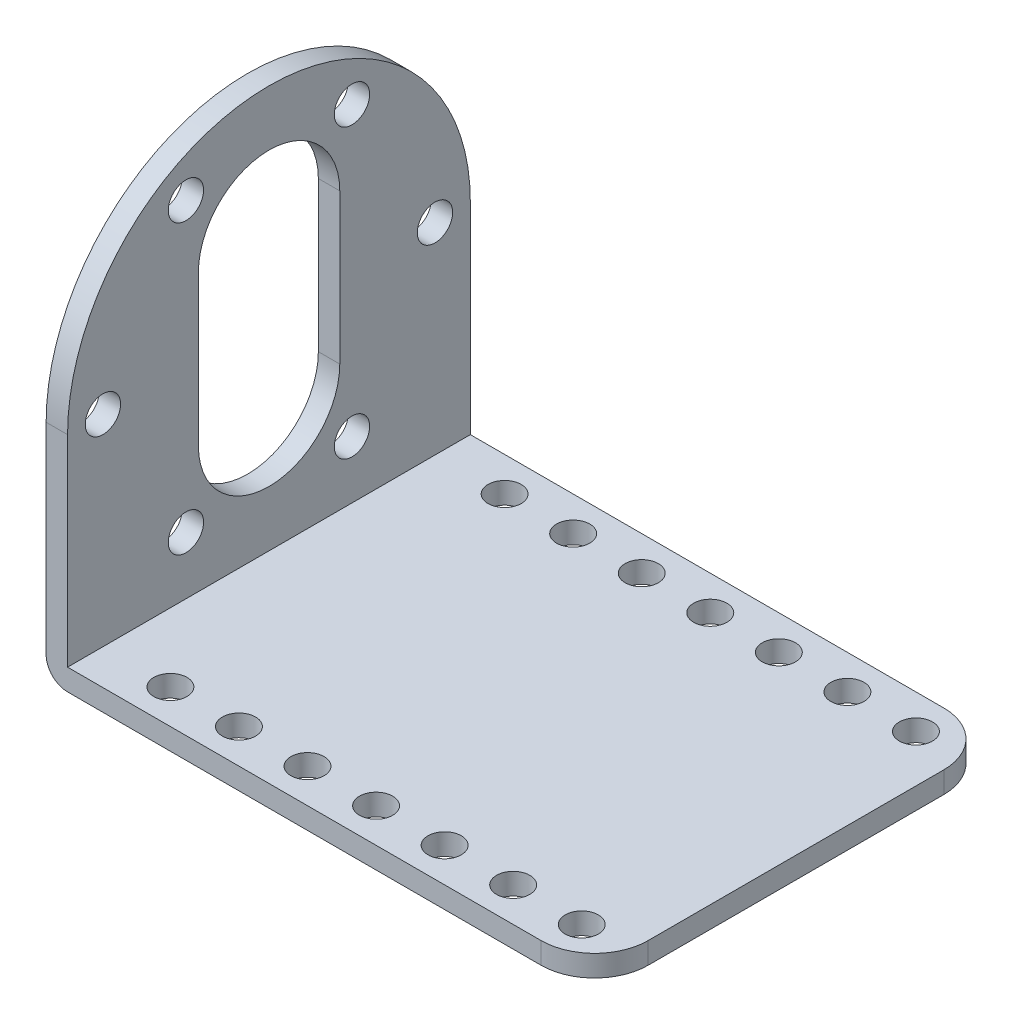
SolidWorks part; units mm, degrees
ref_plane "Front Plane" through (0, 0, 0) normal (0, 0, 1) x (1, 0, 0)
ref_plane "Top Plane" through (0, 0, 0) normal (0, 1, 0) x (1, 0, 0)
ref_plane "Right Plane" through (0, 0, 0) normal (1, 0, 0) x (0, 0, -1)
sketch "Sketch1" plane through (0, 0, 0) normal (0, 1, 0) x (1, 0, 0)
  line L1 (-58.1119, 10.0937) -> (-8.9119, 10.0937)
  line L2 (-58.1119, 10.0937) -> (-58.1119, -27.5063)
  line L3 (-58.1119, -27.5063) -> (-8.9119, -27.5063)
  line L4 (-8.9119, 10.0937) -> (-8.9119, -27.5063)
extrude "Boss-Extrude1" add sketch "Sketch1" along normal blind 2
ref_plane "Side plane L" through (0, 0, 27.5063) normal (0, 0, 1) x (1, 0, 0)
ref_plane "Top face plane" through (0, 2, 0) normal (0, 1, 0) x (1, 0, 0)
sketch "Sketch2" plane through (0, 2, 0) normal (0, 1, 0) x (1, 0, 0)
  line L0 (-1.1, -27.5063) -> (1.1, -27.5063) construction
  line L1 (-58.1119, 10.0937) -> (-60.1119, 10.0937)
  line L2 (-58.1119, 10.0937) -> (-58.1119, -27.5063)
  line L3 (-58.1119, -27.5063) -> (-60.1119, -27.5063)
  line L4 (-60.1119, 10.0937) -> (-60.1119, -27.5063)
extrude "Boss-Extrude2" add sketch "Sketch2" along normal blind 37.6 separate body
sketch "Sketch3" plane through (0, 0, 27.5063) normal (0, 0, 1) x (1, 0, 0)
  line L0 (20.68, 2) -> (-20.68, 2) construction
  line L1 (-58.1119, 2) -> (-58.1119, 0) construction
  line L2 (-60.1119, 2) -> (-58.1119, 2)
  line L3 (-58.1119, 2) -> (-58.1119, 0)
  arc A0 (-60.1119, 2) -> (-58.1119, 0) centre (-58.1119, 2) ccw
ref_plane "Side Plane R" through (0, 0, -10.0937) normal (0, 0, -1) x (-1, 0, 0)
extrude "Boss-Extrude5" add sketch "Sketch3" against normal blind 37.6 contours A0 L3 L2
sketch "Sketch4" plane through (0, 2, 0) normal (0, 1, 0) x (1, 0, 0)
  line L0 (-51.7119, 6.8937) -> (-58.1119, 6.8937) construction
  line L2 (-58.1119, -27.5063) -> (-58.1119, 10.0937) construction
  line L3 (-8.9119, -8.7063) -> (-58.1119, -8.7063) construction
  line L5 (-8.9119, -27.5063) -> (-8.9119, 10.0937) construction
  line L6 (-51.7119, -24.3063) -> (-51.7119, 6.8937) construction
  line L13 (-45.3119, -24.3063) -> (-45.3119, 6.8937) construction
  line L14 (-38.9119, -24.3063) -> (-38.9119, 6.8937) construction
  line L15 (-32.5119, -24.3063) -> (-32.5119, 6.8937) construction
  line L16 (-26.1119, -24.3063) -> (-26.1119, 6.8937) construction
  line L17 (-19.7119, -24.3063) -> (-19.7119, 6.8937) construction
  line L18 (-13.3119, -24.3063) -> (-13.3119, 6.8937) construction
  circle A0 centre (-51.7119, 6.8937) radius 1.55
  circle A1 centre (-51.7119, -24.3063) radius 1.55
  circle A2 centre (-45.3119, 6.8937) radius 1.55
  circle A3 centre (-38.9119, 6.8937) radius 1.55
  circle A4 centre (-32.5119, 6.8937) radius 1.55
  circle A5 centre (-26.1119, 6.8937) radius 1.55
  circle A6 centre (-19.7119, 6.8937) radius 1.55
  circle A7 centre (-13.3119, 6.8937) radius 1.55
  circle A8 centre (-13.3119, -24.3063) radius 1.55
  circle A9 centre (-19.7119, -24.3063) radius 1.55
  circle A10 centre (-26.1119, -24.3063) radius 1.55
  circle A11 centre (-32.5119, -24.3063) radius 1.55
  circle A12 centre (-38.9119, -24.3063) radius 1.55
  circle A13 centre (-45.3119, -24.3063) radius 1.55
  dimension "D1" = 7
extrude "Cut-Extrude1" cut sketch "Sketch4" against normal up to next
fillet "Fillet2" radius 5 2 edges at (-8.9119, 1, 27.5063) (-8.9119, 1, -10.0937)
sketch "Sketch5" plane through (-58.1119, 0, 0) normal (1, 0, 0) x (0, 0, -1)
  line L0 (-8.7063, 2) -> (-8.7063, 20.8) construction
  line L3 (-22.5063, 2) -> (5.0937, 2) construction
  line L4 (-27.5063, 39.6) -> (-27.5063, 2) construction
  line L5 (10.0937, 39.6) -> (10.0937, 2) construction
  circle A0 centre (-8.7063, 20.8) radius 15.5
  circle A1 centre (6.7937, 20.8) radius 1.65
  circle A2 centre (-0.9563, 7.3766) radius 1.65
  circle A3 centre (-16.4563, 7.3766) radius 1.65
  circle A4 centre (-24.2063, 20.8) radius 1.65
  circle A5 centre (-16.4563, 34.2234) radius 1.65
  circle A6 centre (-0.9563, 34.2234) radius 1.65
  arc A7 (-27.5063, 20.8) -> (10.0937, 20.8) centre (-8.7063, 20.8) cw
  point P20 (-8.7063, 20.8)
  dimension "D1" = 6
extrude "Cut-Extrude2" cut sketch "Sketch5" against normal up to next contours A5 | A4 | A3 | A2 | A1 | A6
sketch "Sketch6" plane through (-58.1119, 0, 0) normal (1, 0, 0) x (0, 0, -1)
  line L0 (-8.7063, 2) -> (-8.7063, 20.8) construction
  line L1 (-27.5063, 2) -> (10.0937, 2) construction
  line L2 (-27.5063, 39.6) -> (-27.5063, 2) construction
  line L3 (10.0937, 39.6) -> (10.0937, 2) construction
  arc A0 (-27.5063, 20.8) -> (10.0937, 20.8) centre (-8.7063, 20.8) cw
extrude "Cut-Extrude3" cut sketch "Sketch6" against normal through all and the other way through all
sketch "Sketch8" plane through (-58.1119, 0, 0) normal (1, 0, 0) x (0, 0, -1)
  line L0 (-8.7063, 2) -> (-8.695, 20.8) construction
  line L2 (-8.695, 13.8) -> (-8.695, 27.8) construction
  line L3 (-15.295, 13.8) -> (-15.295, 27.8)
  line L4 (-2.095, 13.8) -> (-2.095, 27.8)
  line L5 (-22.5063, 2) -> (5.0937, 2) construction
  arc A0 (-15.295, 13.8) -> (-2.095, 13.8) centre (-8.695, 13.8) ccw
  arc A1 (-2.095, 27.8) -> (-15.295, 27.8) centre (-8.695, 27.8) ccw
  point P6 (-8.695, 20.8)
extrude "Cut-Extrude4" cut sketch "Sketch8" against normal up to next
